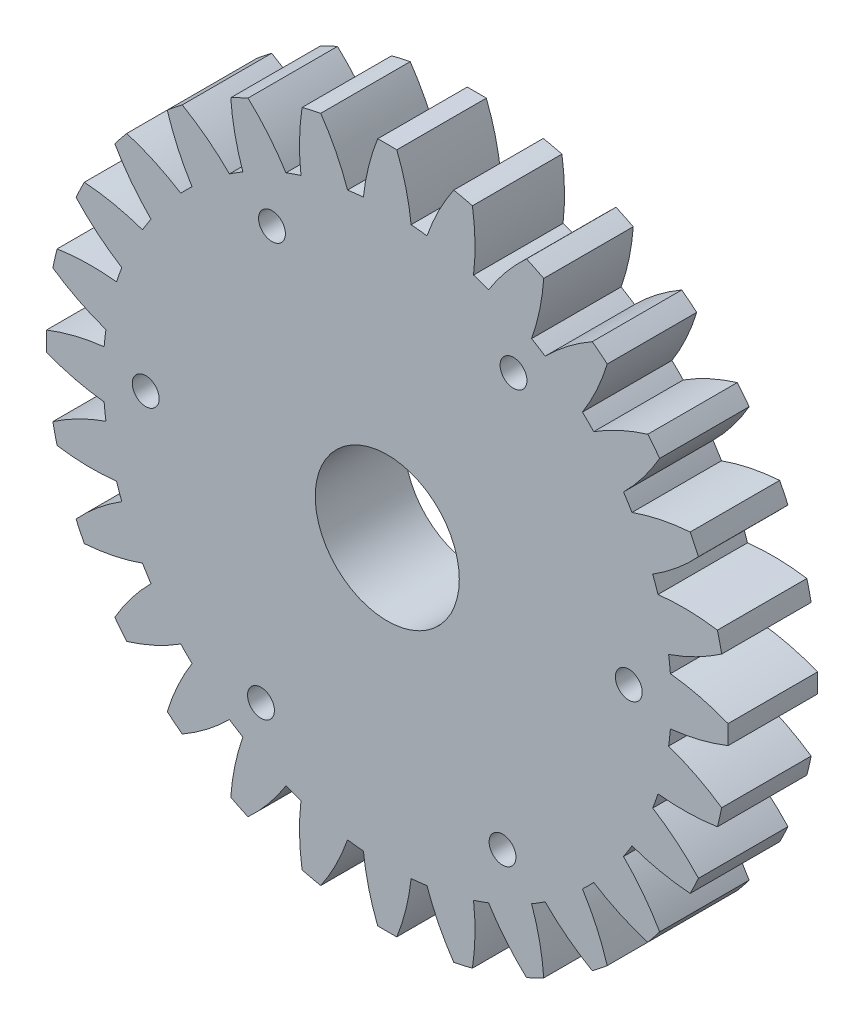
SolidWorks part; units mm, degrees
ref_plane "Front Plane" through (0, 0, 0) normal (0, 0, 1) x (1, 0, 0)
ref_plane "Top Plane" through (0, 0, 0) normal (0, 1, 0) x (1, 0, 0)
ref_plane "Right Plane" through (0, 0, 0) normal (1, 0, 0) x (0, 0, -1)
ref_plane "Plane1" through (0, 0, 5) normal (0, 0, 1) x (1, 0, 0)
sketch "Sketch1" plane through (0, 0, 5) normal (0, 0, 1) x (1, 0, 0)
  line L3 (0, 0) -> (-1.7774, 15.7752) construction
  arc A0 (-4.8209, 15.1253) -> (-5.6614, 14.8312) centre (0, 0) ccw
  arc A1 (-5.6614, 14.8312) -> (-7.7809, 17.3885) centre (-16.2618, 8.2026) ccw
  arc A2 (-7.7809, 17.3885) -> (-8.7436, 16.9249) centre (0, 0) ccw
  arc A3 (-8.7436, 16.9249) -> (-8.0657, 13.6733) centre (3.7261, 17.8282) ccw
  arc A4 (-8.0657, 13.6733) -> (-8.8197, 13.1996) centre (0, 0) ccw
  arc A5 (-8.8197, 13.1996) -> (-11.4551, 15.2211) centre (-17.6794, 4.3783) ccw
  arc A6 (-11.4551, 15.2211) -> (-12.2905, 14.5549) centre (0, 0) ccw
  arc A7 (-12.2905, 14.5549) -> (-10.9061, 11.5357) centre (-0.3345, 18.2104) ccw
  arc A8 (-10.9061, 11.5357) -> (-11.5357, 10.9061) centre (0, 0) ccw
  arc A9 (-11.5357, 10.9061) -> (-14.5549, 12.2905) centre (-18.2104, 0.3345) ccw
  arc A10 (-14.5549, 12.2905) -> (-15.2211, 11.4551) centre (0, 0) ccw
  arc A11 (-15.2211, 11.4551) -> (-13.1996, 8.8197) centre (-4.3783, 17.6794) ccw
  arc A12 (-13.1996, 8.8197) -> (-13.6733, 8.0657) centre (0, 0) ccw
  arc A13 (-13.6733, 8.0657) -> (-16.9249, 8.7436) centre (-17.8282, -3.7261) ccw
  arc A14 (-16.9249, 8.7436) -> (-17.3885, 7.7809) centre (0, 0) ccw
  arc A15 (-17.3885, 7.7809) -> (-14.8312, 5.6614) centre (-8.2026, 16.2618) ccw
  arc A16 (-14.8312, 5.6614) -> (-15.1253, 4.8209) centre (0, 0) ccw
  arc A17 (-15.1253, 4.8209) -> (-18.4462, 4.7582) centre (-16.5521, -7.5998) ccw
  arc A18 (-18.4462, 4.7582) -> (-18.684, 3.7165) centre (0, 0) ccw
  arc A19 (-18.684, 3.7165) -> (-15.7191, 2.2192) centre (-11.6155, 14.0289) ccw
  arc A20 (-15.7191, 2.2192) -> (-15.8188, 1.3343) centre (0, 0) ccw
  arc A21 (-15.8188, 1.3343) -> (-19.0425, 0.5343) centre (-14.446, -11.0924) ccw
  arc A22 (-19.0425, 0.5343) -> (-19.0425, -0.5343) centre (0, 0) ccw
  arc A23 (-19.0425, -0.5343) -> (-15.8188, -1.3343) centre (-14.446, 11.0924) ccw
  arc A24 (-15.8188, -1.3343) -> (-15.7191, -2.2192) centre (0, 0) ccw
  arc A25 (-15.7191, -2.2192) -> (-18.684, -3.7165) centre (-11.6155, -14.0289) ccw
  arc A26 (-18.684, -3.7165) -> (-18.4462, -4.7582) centre (0, 0) ccw
  arc A27 (-18.4462, -4.7582) -> (-15.1253, -4.8209) centre (-16.5521, 7.5998) ccw
  arc A28 (-15.1253, -4.8209) -> (-14.8312, -5.6614) centre (0, 0) ccw
  arc A29 (-14.8312, -5.6614) -> (-17.3885, -7.7809) centre (-8.2026, -16.2618) ccw
  arc A30 (-17.3885, -7.7809) -> (-16.9249, -8.7436) centre (0, 0) ccw
  arc A31 (-16.9249, -8.7436) -> (-13.6733, -8.0657) centre (-17.8282, 3.7261) ccw
  arc A32 (-13.6733, -8.0657) -> (-13.1996, -8.8197) centre (0, 0) ccw
  arc A33 (-13.1996, -8.8197) -> (-15.2211, -11.4551) centre (-4.3783, -17.6794) ccw
  arc A34 (-15.2211, -11.4551) -> (-14.5549, -12.2905) centre (0, 0) ccw
  arc A35 (-14.5549, -12.2905) -> (-11.5357, -10.9061) centre (-18.2104, -0.3345) ccw
  arc A36 (-11.5357, -10.9061) -> (-10.9061, -11.5357) centre (0, 0) ccw
  arc A37 (-10.9061, -11.5357) -> (-12.2905, -14.5549) centre (-0.3345, -18.2104) ccw
  arc A38 (-12.2905, -14.5549) -> (-11.4551, -15.2211) centre (0, 0) ccw
  arc A39 (-11.4551, -15.2211) -> (-8.8197, -13.1996) centre (-17.6794, -4.3783) ccw
  arc A40 (-8.8197, -13.1996) -> (-8.0657, -13.6733) centre (0, 0) ccw
  arc A41 (-8.0657, -13.6733) -> (-8.7436, -16.9249) centre (3.7261, -17.8282) ccw
  arc A42 (-8.7436, -16.9249) -> (-7.7809, -17.3885) centre (0, 0) ccw
  arc A43 (-7.7809, -17.3885) -> (-5.6614, -14.8312) centre (-16.2618, -8.2026) ccw
  arc A44 (-5.6614, -14.8312) -> (-4.8209, -15.1253) centre (0, 0) ccw
  arc A45 (-4.8209, -15.1253) -> (-4.7582, -18.4462) centre (7.5998, -16.5521) ccw
  arc A46 (-4.7582, -18.4462) -> (-3.7165, -18.684) centre (0, 0) ccw
  arc A47 (-3.7165, -18.684) -> (-2.2192, -15.7191) centre (-14.0289, -11.6155) ccw
  arc A48 (-2.2192, -15.7191) -> (-1.3343, -15.8188) centre (0, 0) ccw
  arc A49 (-1.3343, -15.8188) -> (-0.5343, -19.0425) centre (11.0924, -14.446) ccw
  arc A50 (-0.5343, -19.0425) -> (0.5343, -19.0425) centre (0, 0) ccw
  arc A51 (0.5343, -19.0425) -> (1.3343, -15.8188) centre (-11.0924, -14.446) ccw
  arc A52 (1.3343, -15.8188) -> (2.2192, -15.7191) centre (0, 0) ccw
  arc A53 (2.2192, -15.7191) -> (3.7165, -18.684) centre (14.0289, -11.6155) ccw
  arc A54 (3.7165, -18.684) -> (4.7582, -18.4462) centre (0, 0) ccw
  arc A55 (4.7582, -18.4462) -> (4.8209, -15.1253) centre (-7.5998, -16.5521) ccw
  arc A56 (4.8209, -15.1253) -> (5.6614, -14.8312) centre (0, 0) ccw
  arc A57 (5.6614, -14.8312) -> (7.7809, -17.3885) centre (16.2618, -8.2026) ccw
  arc A58 (7.7809, -17.3885) -> (8.7436, -16.9249) centre (0, 0) ccw
  arc A59 (8.7436, -16.9249) -> (8.0657, -13.6733) centre (-3.7261, -17.8282) ccw
  arc A60 (8.0657, -13.6733) -> (8.8197, -13.1996) centre (0, 0) ccw
  arc A61 (8.8197, -13.1996) -> (11.4551, -15.2211) centre (17.6794, -4.3783) ccw
  arc A62 (11.4551, -15.2211) -> (12.2905, -14.5549) centre (0, 0) ccw
  arc A63 (12.2905, -14.5549) -> (10.9061, -11.5357) centre (0.3345, -18.2104) ccw
  arc A64 (10.9061, -11.5357) -> (11.5357, -10.9061) centre (0, 0) ccw
  arc A65 (11.5357, -10.9061) -> (14.5549, -12.2905) centre (18.2104, -0.3345) ccw
  arc A66 (14.5549, -12.2905) -> (15.2211, -11.4551) centre (0, 0) ccw
  arc A67 (15.2211, -11.4551) -> (13.1996, -8.8197) centre (4.3783, -17.6794) ccw
  arc A68 (13.1996, -8.8197) -> (13.6733, -8.0657) centre (0, 0) ccw
  arc A69 (13.6733, -8.0657) -> (16.9249, -8.7436) centre (17.8282, 3.7261) ccw
  arc A70 (16.9249, -8.7436) -> (17.3885, -7.7809) centre (0, 0) ccw
  arc A71 (17.3885, -7.7809) -> (14.8312, -5.6614) centre (8.2026, -16.2618) ccw
  arc A72 (14.8312, -5.6614) -> (15.1253, -4.8209) centre (0, 0) ccw
  arc A73 (15.1253, -4.8209) -> (18.4462, -4.7582) centre (16.5521, 7.5998) ccw
  arc A74 (18.4462, -4.7582) -> (18.684, -3.7165) centre (0, 0) ccw
  arc A75 (18.684, -3.7165) -> (15.7191, -2.2192) centre (11.6155, -14.0289) ccw
  arc A76 (15.7191, -2.2192) -> (15.8188, -1.3343) centre (0, 0) ccw
  arc A77 (15.8188, -1.3343) -> (19.0425, -0.5343) centre (14.446, 11.0924) ccw
  arc A78 (19.0425, -0.5343) -> (19.0425, 0.5343) centre (0, 0) ccw
  arc A79 (19.0425, 0.5343) -> (15.8188, 1.3343) centre (14.446, -11.0924) ccw
  arc A80 (15.8188, 1.3343) -> (15.7191, 2.2192) centre (0, 0) ccw
  arc A81 (15.7191, 2.2192) -> (18.684, 3.7165) centre (11.6155, 14.0289) ccw
  arc A82 (18.684, 3.7165) -> (18.4462, 4.7582) centre (0, 0) ccw
  arc A83 (18.4462, 4.7582) -> (15.1253, 4.8209) centre (16.5521, -7.5998) ccw
  arc A84 (15.1253, 4.8209) -> (14.8312, 5.6614) centre (0, 0) ccw
  arc A85 (14.8312, 5.6614) -> (17.3885, 7.7809) centre (8.2026, 16.2618) ccw
  arc A86 (17.3885, 7.7809) -> (16.9249, 8.7436) centre (0, 0) ccw
  arc A87 (16.9249, 8.7436) -> (13.6733, 8.0657) centre (17.8282, -3.7261) ccw
  arc A88 (13.6733, 8.0657) -> (13.1996, 8.8197) centre (0, 0) ccw
  arc A89 (13.1996, 8.8197) -> (15.2211, 11.4551) centre (4.3783, 17.6794) ccw
  arc A90 (15.2211, 11.4551) -> (14.5549, 12.2905) centre (0, 0) ccw
  arc A91 (14.5549, 12.2905) -> (11.5357, 10.9061) centre (18.2104, 0.3345) ccw
  arc A92 (11.5357, 10.9061) -> (10.9061, 11.5357) centre (0, 0) ccw
  arc A93 (10.9061, 11.5357) -> (12.2905, 14.5549) centre (0.3345, 18.2104) ccw
  arc A94 (12.2905, 14.5549) -> (11.4551, 15.2211) centre (0, 0) ccw
  arc A95 (11.4551, 15.2211) -> (8.8197, 13.1996) centre (17.6794, 4.3783) ccw
  arc A96 (8.8197, 13.1996) -> (8.0657, 13.6733) centre (0, 0) ccw
  arc A97 (8.0657, 13.6733) -> (8.7436, 16.9249) centre (-3.7261, 17.8282) ccw
  arc A98 (8.7436, 16.9249) -> (7.7809, 17.3885) centre (0, 0) ccw
  arc A99 (7.7809, 17.3885) -> (5.6614, 14.8312) centre (16.2618, 8.2026) ccw
  arc A100 (5.6614, 14.8312) -> (4.8209, 15.1253) centre (0, 0) ccw
  arc A101 (4.8209, 15.1253) -> (4.7582, 18.4462) centre (-7.5998, 16.5521) ccw
  arc A102 (4.7582, 18.4462) -> (3.7165, 18.684) centre (0, 0) ccw
  arc A103 (3.7165, 18.684) -> (2.2192, 15.7191) centre (14.0289, 11.6155) ccw
  arc A104 (2.2192, 15.7191) -> (1.3343, 15.8188) centre (0, 0) ccw
  arc A105 (1.3343, 15.8188) -> (0.5343, 19.0425) centre (-11.0924, 14.446) ccw
  arc A106 (0.5343, 19.0425) -> (-0.5343, 19.0425) centre (0, 0) ccw
  arc A107 (-0.5343, 19.0425) -> (-1.3343, 15.8188) centre (11.0924, 14.446) ccw
  arc A108 (-1.3343, 15.8188) -> (-2.2192, 15.7191) centre (0, 0) ccw
  arc A109 (-2.2192, 15.7191) -> (-3.7165, 18.684) centre (-14.0289, 11.6155) ccw
  arc A110 (-3.7165, 18.684) -> (-4.7582, 18.4462) centre (0, 0) ccw
  arc A111 (-4.7582, 18.4462) -> (-4.8209, 15.1253) centre (7.5998, 16.5521) ccw
  circle A112 centre (0, 0) radius 4.025
  circle A113 centre (-6.4405, 11.8647) radius 0.75
  circle A114 centre (7.0548, 11.51) radius 0.75
  circle A115 centre (13.4953, -0.3547) radius 0.75
  circle A116 centre (6.4405, -11.8647) radius 0.75
  circle A117 centre (-7.0548, -11.51) radius 0.75
  circle A118 centre (-13.4953, 0.3547) radius 0.75
  point P186 (0, 0)
  dimension "D2" = 8.05
  dimension "D1" = 19.05
  dimension "D3" = 1.5
  dimension "D4" = 13.5
  dimension "D5" = 6
extrude "Boss-Extrude1" add sketch "Sketch1" against normal blind 5
ref_axis "Axis1" through (0, 0, 0) along (0, 0, 1)
sketch "Sketch2" [suppressed] plane through (0, 0, 5) normal (0, 0, 1) x (1, 0, 0)
  line L0 (0, 0) -> (0, 19.05) construction
  line L1 (0, 0) -> (-1.7774, -15.7752) construction
  line L2 (0, 0) -> (5.2432, 14.9841) construction
  arc A0 (0.5343, 19.0425) -> (-0.5343, 19.0425) centre (0, 0) ccw construction
  arc A1 (-2.2192, -15.7191) -> (-1.3343, -15.8188) centre (0, 0) ccw construction
  arc A2 (5.6614, 14.8312) -> (4.8209, 15.1253) centre (0, 0) ccw construction
